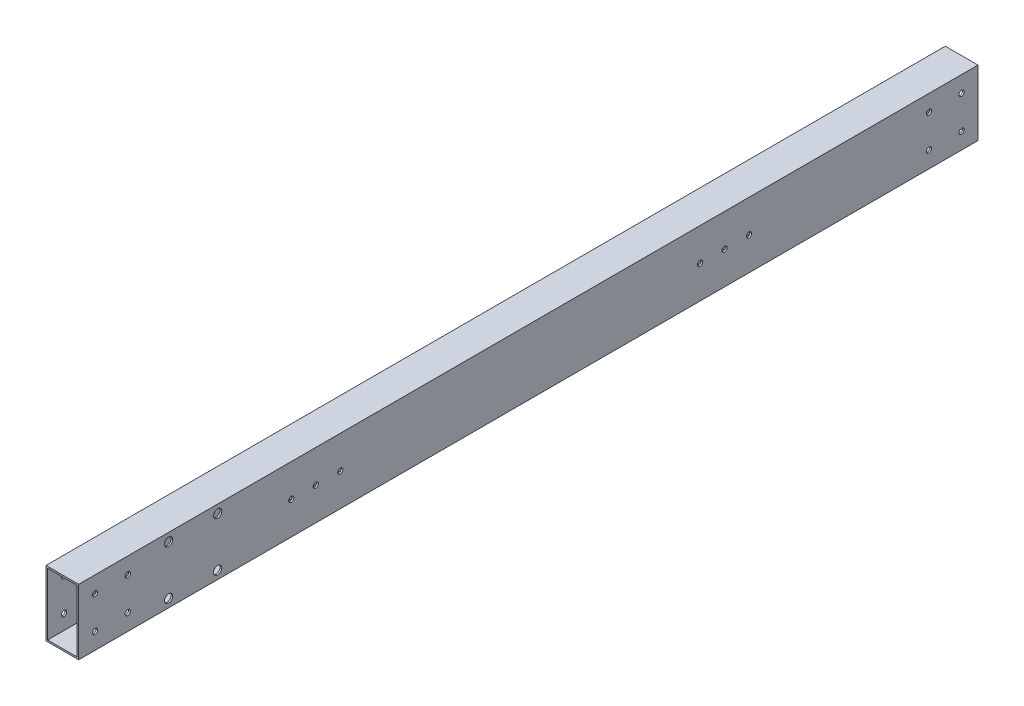
SolidWorks part; units mm, degrees
material "1060 合金"
ref_plane "前视基准面" through (0, 0, 0) normal (0, 0, 1) x (1, 0, 0)
ref_plane "上视基准面" through (0, 0, 0) normal (0, 1, 0) x (1, 0, 0)
ref_plane "右视基准面" through (0, 0, 0) normal (1, 0, 0) x (0, 0, -1)
other "Configuration Table"
sketch "草图1" plane through (0, 0, 0) normal (0, 0, 1) x (1, 0, 0)
  line L1 (0, 0) -> (20, 0)
  line L2 (0, 0) -> (0, -40)
  line L3 (0, -40) -> (20, -40)
  line L4 (20, 0) -> (20, -40)
  dimension "D1" = 40
  dimension "D2" = 20
extrude "拉伸-薄壁1" add sketch "草图1" along normal blind 550 thin thin type one direction reverse wall 1
sketch "草图2" plane through (0, 0, 0) normal (-1, 0, 0) x (0, 0, 1)
  line L0 (550, -40) -> (0, -40) construction
  line L1 (550, 0) -> (550, -40) construction
  circle A0 centre (420, -20) radius 1.6
  circle A1 centre (405, -20) radius 1.6
  circle A2 centre (390, -20) radius 1.6
  circle A3 centre (140, -20) radius 1.6
  circle A4 centre (155, -20) radius 1.6
  circle A5 centre (170, -20) radius 1.6
  dimension "D1" = 3.2
  dimension "D2" = 20
  dimension "D3" = 130
  dimension "D4" = 3
  dimension "D5" = 2
extrude "切除-拉伸1" cut sketch "草图2" against normal through all
sketch "草图3" plane through (0, 0, 0) normal (-1, 0, 0) x (0, 0, 1)
  line L0 (550, -40) -> (0, -40) construction
  line L1 (550, 0) -> (550, -40) construction
  circle A0 centre (495, -35) radius 2.5
  circle A1 centre (465, -35) radius 2.5
  circle A2 centre (465, -5) radius 2.5
  circle A3 centre (495, -5) radius 2.5
  dimension "D1" = 5
  dimension "D2" = 5
  dimension "D3" = 55
  dimension "D4" = 2
  dimension "D5" = 2
extrude "切除-拉伸2" cut sketch "草图3" against normal through all
sketch "草图4" plane through (0, -40, 0) normal (0, -1, 0) x (1, 0, 0)
  line L0 (0, 550) -> (0, 0) construction
  line L1 (0, 0) -> (20, 0) construction
  circle A0 centre (10, 50) radius 1.75
  circle A1 centre (10, 70) radius 1.75
  circle A2 centre (10, 90) radius 1.75
  circle A3 centre (10, 110) radius 1.75
  circle A4 centre (10, 130) radius 1.75
  circle A5 centre (10, 150) radius 1.75
  circle A6 centre (10, 170) radius 1.75
  circle A7 centre (10, 190) radius 1.75
  circle A8 centre (10, 210) radius 1.75
  circle A9 centre (10, 230) radius 1.75
  circle A10 centre (10, 250) radius 1.75
  circle A11 centre (10, 270) radius 1.75
  circle A12 centre (10, 290) radius 1.75
  circle A13 centre (10, 310) radius 1.75
  circle A14 centre (10, 330) radius 1.75
  circle A15 centre (10, 350) radius 1.75
  circle A16 centre (10, 370) radius 1.75
  circle A17 centre (10, 390) radius 1.75
  circle A18 centre (10, 410) radius 1.75
  circle A19 centre (10, 430) radius 1.75
  circle A20 centre (10, 450) radius 1.75
  circle A21 centre (10, 470) radius 1.75
  circle A22 centre (10, 490) radius 1.75
  dimension "D1" = 3.5
  dimension "D2" = 10
  dimension "D3" = 50
  dimension "D4" = 23
extrude "切除-拉伸3" cut sketch "草图4" against normal up to next
sketch "草图5" plane through (0, 0, 0) normal (-1, 0, 0) x (0, 0, 1)
  line L0 (550, 0) -> (550, -40) construction
  line L1 (550, 0) -> (0, 0) construction
  circle A0 centre (540, -10) radius 1.6
  circle A1 centre (540, -30) radius 1.6
  circle A2 centre (520, -30) radius 1.6
  circle A3 centre (520, -10) radius 1.6
  circle A4 centre (10, -10) radius 1.6
  circle A5 centre (30, -10) radius 1.6
  circle A6 centre (10, -30) radius 1.6
  circle A7 centre (30, -30) radius 1.6
  dimension "D1" = 3.2
  dimension "D2" = 10
  dimension "D3" = 10
  dimension "D4" = 2
  dimension "D5" = 2
  dimension "D6" = 2
extrude "切除-拉伸4" cut sketch "草图5" against normal through all
